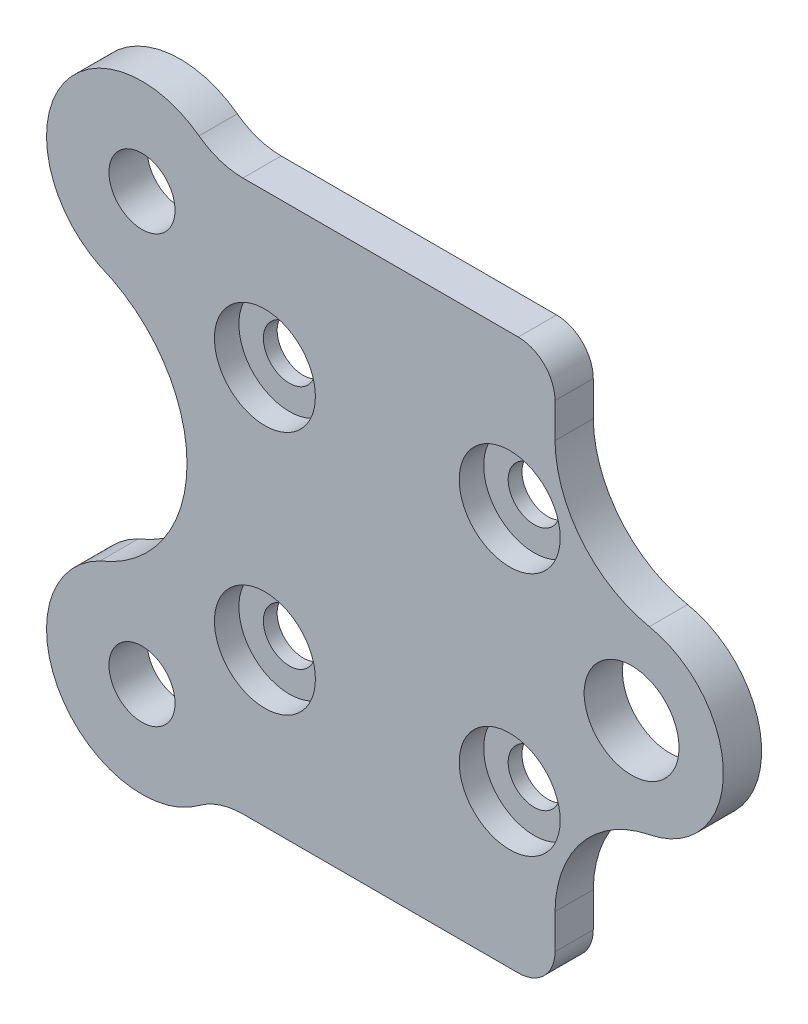
SolidWorks part; units mm, degrees
ref_plane "Front Plane" through (0, 0, 0) normal (0, 0, 1) x (1, 0, 0)
ref_plane "Top Plane" through (0, 0, 0) normal (0, 1, 0) x (1, 0, 0)
ref_plane "Right Plane" through (0, 0, 0) normal (1, 0, 0) x (0, 0, -1)
sketch "Model" plane through (0, 0, 0) normal (0, 0, 1) x (1, 0, 0)
  line L0 (57.9402, 39.9305) -> (85.7512, 39.9305)
  line L2 (85.7512, 0.7699) -> (85.7512, -5.0695)
  line L3 (85.7512, 39.9305) -> (85.7512, 34.0911)
  line L4 (57.9402, -5.0695) -> (85.7512, -5.0695)
  arc A0 (48.5736, 27.8627) -> (57.9402, 39.9305) centre (52.0082, 34.8658) cw
  circle A1 centre (92.0082, 17.4305) radius 3.875
  circle A2 centre (52.0082, -0.0048) radius 2.7
  circle A3 centre (52.0082, 34.8658) radius 2.7
  circle A4 centre (82.0501, 7.4305) radius 2.125
  circle A5 centre (62.0501, 7.4305) radius 2.125
  circle A6 centre (82.0501, 27.4305) radius 2.125
  circle A7 centre (62.0501, 27.4305) radius 2.125
  arc A8 (48.5736, 6.9983) -> (57.9402, -5.0695) centre (52.0082, -0.0048) ccw
  arc A11 (93.4574, 10.0719) -> (85.7512, 0.7699) centre (95.3556, 0.6562) ccw
  arc A12 (93.4574, 10.0719) -> (93.4574, 24.7892) centre (92.0082, 17.4305) ccw
  arc A13 (85.7512, 34.0911) -> (93.4574, 24.7892) centre (95.3556, 34.2048) ccw
  arc A16 (48.5736, 6.9983) -> (48.5736, 27.8627) centre (44.48, 17.4305) ccw
  circle A22 centre (62.0501, 27.4305) radius 4.125
  circle A23 centre (62.0501, 7.4305) radius 4.125
  circle A24 centre (82.0501, 27.4305) radius 4.125
  circle A25 centre (82.0501, 7.4305) radius 4.125
  dimension "D2" = 7.75
  dimension "D3" = 8.25
  dimension "D4" = 4.25
  dimension "D5" = 5.4
  dimension "D6" = 34.8706
  dimension "D7" = 9.9581
  dimension "D8" = 22.5
  dimension "D9" = 22.5
  dimension "D11" = 11.2066
  dimension "D12" = 7.8
  dimension "D18" = 9.6051
  dimension "D19" = 7.5
  dimension "D10" = 40
  dimension "D13" = 20
  dimension "D14" = 10
  dimension "D15" = 19.9999
  dimension "D16" = 47.5282
  dimension "D17" = 6.257
  dimension "D20" = 3.3474
  dimension "D21" = 16.7743
extrude "Boss-Extrude1" add sketch "Model" against normal blind 3.125 contours A3 | A2 | A1 | A7 | A6 | A4 | A5 | L4 L2 A11 A12 A13 L3 L0 A0 A16 A8 region at (92.0082, 17.4305, 0) region at (52.0082, -0.0048, 0) region at (52.0082, 34.8658, 0) region at (82.0501, 7.4305, 0) region at (62.0501, 7.4305, 0) region at (82.0501, 27.4305, 0) region at (62.0501, 27.4305, 0)
extrude "Cut-Extrude1" cut sketch "Model<3>" against normal blind 2 contours A25 A4 | A23 A5 | A22 A7 | A24 region at (58.0418, 27.4305, 0) region at (58.0418, 7.4305, 0) region at (78.0417, 7.4305, 0)
sketch "Model<3>" plane through (0, 0, 0) normal (0, 0, 1) x (1, 0, 0) same geometry as "Model"
fillet "Fillet1" radius 3 2 edges at (85.7512, -5.0695, -1.5625) (85.7512, 39.9305, -1.5625)
fillet "Fillet2" radius 6 2 edges at (57.9402, 39.9305, -1.5625) (57.9402, -5.0695, -1.5625)
